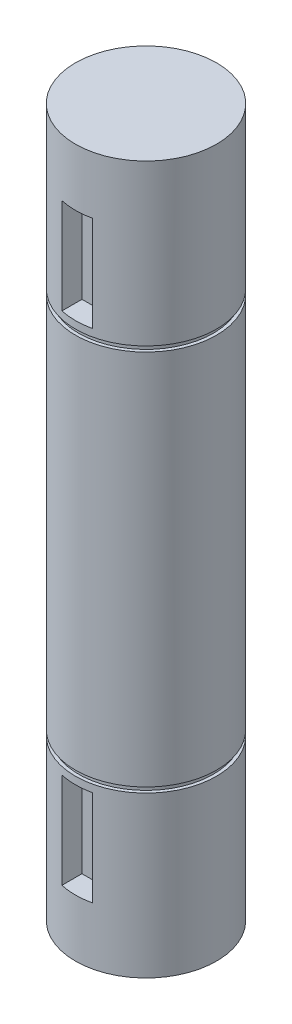
SolidWorks part; units mm, degrees
ref_plane "Front Plane" through (0, 0, 0) normal (0, 0, 1) x (1, 0, 0)
ref_plane "Top Plane" through (0, 0, 0) normal (0, 1, 0) x (1, 0, 0)
ref_plane "Right Plane" through (0, 0, 0) normal (1, 0, 0) x (0, 0, -1)
sketch "Sketch1" plane through (0, 0, 0) normal (0, 1, 0) x (1, 0, 0)
  circle A0 centre (0, 0) radius 32.5
  dimension "D1" = 65
extrude "Boss-Extrude1" add sketch "Sketch1" along normal blind 326
ref_plane "Plane1" through (0, 252.2, 0) normal (0, -1, 0) x (-1, 0, 0)
ref_plane "Plane2" through (0, 73.8, 0) normal (0, 1, 0) x (1, 0, 0)
sketch "Sketch2" plane through (0, 73.8, 0) normal (0, 1, 0) x (1, 0, 0)
  circle A0 centre (0, 0) radius 31
  circle A1 centre (0, 0) radius 53.4531
  dimension "D1" = 62
extrude "Cut-Extrude1" cut sketch "Sketch2" along normal blind 2.42
sketch "Sketch3" plane through (0, 252.2, 0) normal (0, -1, 0) x (-1, 0, 0)
  circle A0 centre (0, 0) radius 31
  circle A1 centre (0, 0) radius 95.953
  dimension "D1" = 62
extrude "Cut-Extrude2" cut sketch "Sketch3" along normal blind 2.42
ref_plane "Plane3" through (0, 23, 0) normal (0, -1, 0) x (-1, 0, 0)
ref_plane "Plane4" through (0, 303, 0) normal (0, 1, 0) x (1, 0, 0)
ref_plane "Plane5" through (0, 0, 32.5) normal (0, 0, 1) x (1, 0, 0)
ref_plane "Plane6" through (0, 163, 0) normal (0, -1, 0) x (-1, 0, 0)
ref_axis "Axis1" through (0, 402.4693, 0) along (0, -1, 0)
sketch "Sketch5" plane through (0, 0, 32.5) normal (0, 0, 1) x (1, 0, 0)
  line L0 (0, 303) -> (0, 252.2) construction
  line L1 (426.116, 303) -> (-426.116, 303) construction
  line L2 (0, 402.4693) -> (0, 0) construction
  line L3 (-31, 252.2) -> (31, 252.2) construction
  line L4 (-55, 163) -> (55, 163) construction
  line L5 (-7, 299.6) -> (7, 299.6)
  line L6 (-7, 299.6) -> (-7, 255.6)
  line L7 (-7, 255.6) -> (7, 255.6)
  line L8 (7, 299.6) -> (7, 255.6)
  line L9 (-7, 299.6) -> (7, 255.6) construction
  line L10 (-7, 255.6) -> (7, 299.6) construction
  line L11 (-7, 70.4) -> (7, 70.4)
  line L12 (-7, 26.4) -> (7, 26.4)
  line L13 (7, 26.4) -> (7, 70.4)
  line L14 (-7, 26.4) -> (-7, 70.4)
  point P9 (0, 277.6)
  dimension "D1" = 14
  dimension "D2" = 44
extrude "Cut-Extrude3" cut sketch "Sketch5" against normal blind 10
